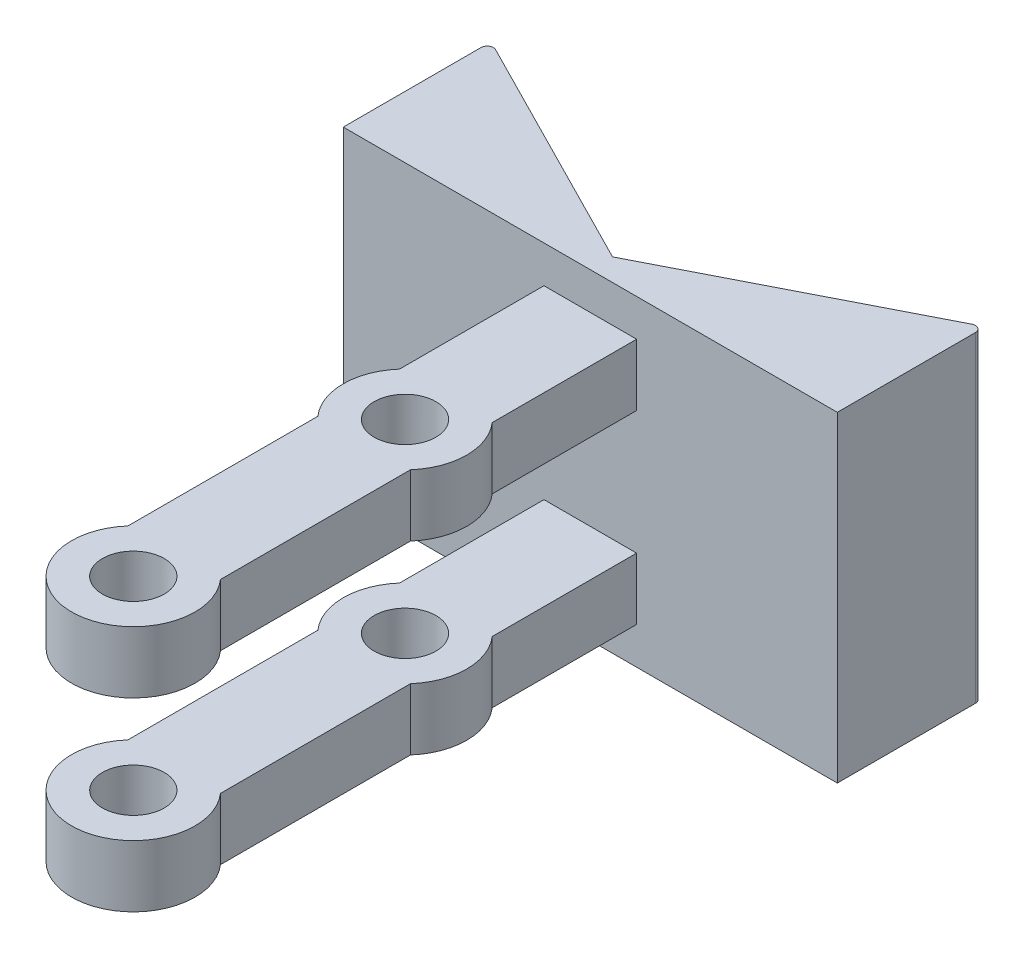
SolidWorks part; units mm, degrees
ref_plane "Front Plane" through (0, 0, 0) normal (0, 0, 1) x (1, 0, 0)
ref_plane "Top Plane" through (0, 0, 0) normal (0, 1, 0) x (1, 0, 0)
ref_plane "Right Plane" through (0, 0, 0) normal (1, 0, 0) x (0, 0, -1)
sketch "Sketch1" plane through (0, 0, 0) normal (0, 1, 0) x (1, 0, 0)
  line L0 (0, 14.0188) -> (0, -24.3344) construction
  line L1 (-20, 9.3344) -> (20, 9.3344)
  line L2 (-20, 9.3344) -> (-20, -9.3344)
  line L3 (-20, -9.3344) -> (-3.75, -9.3344)
  line L4 (20, 9.3344) -> (20, -9.3344)
  line L5 (-20, 9.3344) -> (20, -9.3344) construction
  line L6 (-20, -9.3344) -> (20, 9.3344) construction
  line L7 (-3.75, -9.3344) -> (-3.75, -21.0272)
  line L9 (3.75, -43.0272) -> (3.75, -27.6416)
  line L10 (3.75, -9.3344) -> (20, -9.3344)
  line L11 (-3.75, -27.6416) -> (-3.75, -43.0272)
  line L12 (3.75, -21.0272) -> (3.75, -9.3344)
  arc A0 (-3.75, -21.0272) -> (-3.75, -27.6416) centre (0, -24.3344) ccw
  arc A1 (-3.75, -43.0272) -> (3.75, -43.0272) centre (0, -46.3344) ccw
  circle A2 centre (0, -24.3344) radius 2.5
  circle A3 centre (0, -46.3344) radius 2.5
  arc A4 (3.75, -27.6416) -> (3.75, -21.0272) centre (0, -24.3344) ccw
  point P0 (0, 0)
  dimension "D1" = 40
  dimension "D2" = 22
  dimension "D3" = 15
extrude "Boss-Extrude1" add sketch "Sketch1" along normal blind 20
ref_plane "Plane1" through (0, 10, 0) normal (0, 1, 0) x (1, 0, 0)
sketch "Sketch2" plane through (0, 10, 0) normal (0, 1, 0) x (1, 0, 0)
  line L0 (-11.875, -9.3344) -> (11.875, -9.3344)
  line L1 (-20, -9.3344) -> (-3.75, -9.3344) construction
  line L2 (3.75, -9.3344) -> (20, -9.3344) construction
  line L3 (11.875, -9.3344) -> (11.875, -57.7647)
  line L4 (11.875, -57.7647) -> (-11.875, -57.7647)
  line L5 (-11.875, -57.7647) -> (-11.875, -9.3344)
extrude "Cut-Extrude1" cut sketch "Sketch2" against normal blind 5 and the other way blind 5
sketch "Sketch3" plane through (0, 0, 9.3344) normal (0, 0, 1) x (1, 0, 0)
  line L0 (-20, 20) -> (20, 20)
  line L1 (20, 20) -> (20, 23)
  line L2 (20, 23) -> (-20, 23)
  line L3 (-20, 23) -> (-20, 20)
extrude "Boss-Extrude2" add sketch "Sketch3" against normal up to surface (18.6688 mm away) up to face at (0, 10, -9.3344)
mirror "Mirror1" about plane through (0, 10, 0) normal (0, 1, 0) of "Boss-Extrude2"
sketch "Sketch4" plane through (0, 23, 0) normal (0, 1, 0) x (1, 0, 0)
  line L0 (0, 12.1528) -> (0, -12.7794) construction
  line L1 (-27.0292, 2.6656) -> (23.0416, 2.6656) construction
  line L2 (20, -9.3344) -> (-20, -9.3344) construction
  line L3 (-20.0606, 2.6656) -> (0, -7.5344)
  line L4 (0, -7.5344) -> (19.9961, 2.6656)
  line L5 (19.9961, 2.6656) -> (20, 9.3344)
  line L6 (20, 9.3344) -> (-20, 9.3344)
  line L7 (-20, 9.3344) -> (-20.0606, 2.6656)
  dimension "D1" = 12
  dimension "D2" = 12
  dimension "D3" = 1.8
extrude "Cut-Extrude2" cut sketch "Sketch4" against normal through all
sketch "Sketch5" plane through (19.9945, 0, 0.0118) normal (-1, 0, -0.0006) x (-0.0006, 0, 1)
  line L0 (-2.6774, -3) -> (-2.6774, 23)
  line L1 (-2.6774, 23) -> (-9.3462, 23)
  line L2 (-9.3462, 23) -> (-9.3462, -3)
  line L3 (-9.3462, -3) -> (-2.6774, -3)
extrude "Cut-Extrude3" cut sketch "Sketch5" against normal blind 20
fillet "Fillet1" radius 0.5 2 edges at (-20, 10, -2.6348) (20, 10, -2.6656)
fillet "Fillet3" radius 0.5 1 edges at (19.9961, 10, -2.6656)
